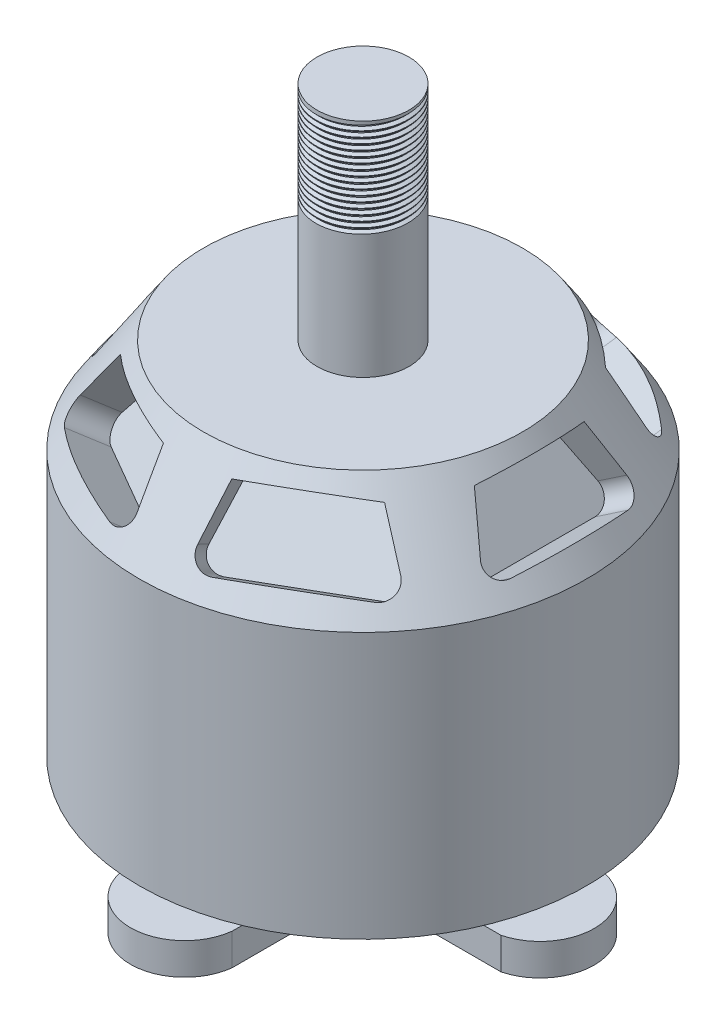
SolidWorks part; units mm, degrees
ref_plane "Front" through (0, 0, 0) normal (0, 0, 1) x (1, 0, 0)
ref_plane "Top" through (0, 0, 0) normal (0, 1, 0) x (1, 0, 0)
ref_plane "Right" through (0, 0, 0) normal (1, 0, 0) x (0, 0, -1)
sketch "草图1" plane through (0, 0, 0) normal (0, 1, 0) x (1, 0, 0)
  circle A0 centre (0, 0) radius 14.1
extrude "凸台-拉伸1" add sketch "草图1" along normal blind 26.8
sketch "草图2" plane through (0, 26.8, 0) normal (0, 1, 0) x (1, 0, 0)
  circle A0 centre (0, 0) radius 2.9
extrude "凸台-拉伸2" add sketch "草图2" along normal blind 14
chamfer "倒角1" distance 6 angle 34 2 edges at (0, 0, 14.1) (0, 26.8, 14.1) first distance on face at (0, 0, 14.1) first distance on face at (0, 26.8, 14.1)
ref_plane "基准面1" through (19.3337, 13.0407, 0) normal (0.829, 0.5592, 0) x (0, 0, -1)
sketch "草图3" plane through (19.3337, 13.0407, 0) normal (0.829, 0.5592, 0) x (0, 0, -1)
  line L0 (-4.9483, 11.0315) -> (-3.2935, 15.5029)
  line L1 (-4.9483, 11.0315) -> (5.3863, 11.0315)
  line L3 (-3.2935, 15.5029) -> (3.7315, 15.5029)
  line L5 (0.219, 15.5029) -> (0.219, 11.0315) construction
  line L6 (5.3863, 11.0315) -> (3.7315, 15.5029)
extrude "切除-拉伸1" cut sketch "草图3" against normal blind 3
ref_axis "基准轴1" through (0, 40.8, 0) along (0, -1, 0)
fillet "圆角1" radius 1 1 edges at (11.5366, 21.088, -5.3863) type face fillet first side face at (11.7439, 21.2278, -0.2207) second side face at (10.6384, 22.5047, -4.7657)
fillet "圆角2" radius 1 1 edges at (11.5975, 21.129, 4.9483) type face fillet first side face at (10.1454, 23.5205, 3.914) second side face at (11.7874, 21.2571, 0.5019)
thread "螺纹线1" pitch 0.3528 method cut profile "螺纹线轮廓1" start angle 0, offset 0, length 6, pitch 0.3528, diameter 5.8
ref_plane "基准面2" through (-2.9, 40.8, 0) normal (0, 0, 1) x (-1, 0, 0)
sketch "螺纹线轮廓1" plane through (-2.9, 40.8, 0) normal (0, 0, 1) x (-1, 0, 0)
  line L0 (0, 0) -> (0, 0.3528) construction
  line L11 (0, 0) -> (0, 0.3087)
  line L12 (0, 0.3087) -> (-0.1909, 0.1984)
  line L13 (-0.1909, 0.1984) -> (-0.1909, 0.1102)
  line L15 (-0.1909, 0.1102) -> (0, 0)
  line L17 (-0.1909, 0.1543) -> (0, 0.1543) construction
  point P2 (0, 0)
  dimension "Pitch" = 0.3528
  dimension "Profile_Angle" = 60
  dimension "Profile_Land" = 0.0882
  dimension "Profile_Height" = 0.1909
pattern_circular "阵列(圆周)2" count 6 every 60 about axis through (0, 40.8, 0) along (0, -1, 0) of "圆角2", "圆角1", "切除-拉伸1"
sketch "草图10" plane through (0, 0, 0) normal (0, -1, 0) x (1, 0, 0)
  line L5 (3.3517, 0) -> (-3.3517, 0)
  line L6 (3.3517, 0) -> (3.3517, 11.6065)
  line L8 (-3.3517, 0) -> (-3.3517, 12.0468)
  arc A0 (-3.3517, 12.0468) -> (3.3517, 11.6065) centre (-0.0409, 11.2039) cw
  point P4 (0, 0)
extrude "凸台-拉伸3" add sketch "草图10" against normal blind 2
pattern_circular "阵列(圆周)3" count 4 every 90 about axis through (0, 40.8, 0) along (0, -1, 0) of "凸台-拉伸3"
sketch "草图11" plane through (0, 0, 0) normal (0, -1, 0) x (1, 0, 0)
  line L0 (0, 0) -> (0, -9.5) construction
  line L1 (0, 0) -> (-8, 0) construction
  circle A0 centre (0, 0) radius 3
  circle A1 centre (-8, 0) radius 1.52
  circle A2 centre (0, -9.5) radius 1.52
  circle A3 centre (0, 9.5) radius 1.52
  circle A4 centre (8, 0) radius 1.52
extrude "切除-拉伸2" cut sketch "草图11" against normal blind 3
